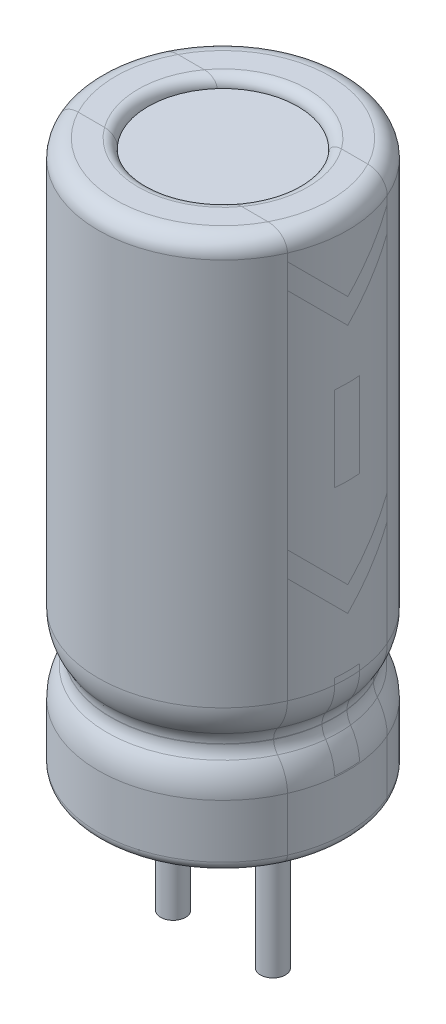
SolidWorks part; units mm, degrees
ref_plane "Front Plane" through (0, 0, 0) normal (0, 0, 1) x (1, 0, 0)
ref_plane "Top Plane" through (0, 0, 0) normal (0, 1, 0) x (1, 0, 0)
ref_plane "Right Plane" through (0, 0, 0) normal (1, 0, 0) x (0, 0, -1)
sketch "Эскиз1" plane through (0, 0, 0) normal (0, 0, 1) x (1, 0, 0)
  line L0 (0, 39.0662) -> (0, -46.657) construction
  line L1 (-41.2396, 0) -> (33.4802, 0) construction
  line L2 (0, 0) -> (-2.5, 0)
  line L3 (-2.5, 0) -> (-2.5, 1.7)
  line L4 (-2.5, 1.7) -> (-2.25, 1.7)
  line L5 (-2.25, 1.7) -> (-2.25, 2.45)
  line L6 (-2.25, 2.45) -> (-2.5, 2.45)
  line L7 (-2.5, 2.45) -> (-2.5, 11)
  line L8 (-2.5, 11) -> (0, 11)
  line L9 (0, 11) -> (0, 0)
  dimension "D1" = 2.5
  dimension "D2" = 11
  dimension "D3" = 1.7
  dimension "D4" = 0.75
  dimension "D5" = 2.5
  dimension "D6" = 0.25
revolve "Повернуть2" add sketch "Эскиз1" angle 360 about L0
fillet "Скругление12" radius 0.4 2 edges at (0, 2.45, 2.25) (0, 1.7, 2.25)
fillet "Скругление13" radius 1 1 edges at (0, 2.45, 2.5)
fillet "Скругление14" radius 1 1 edges at (0, 1.7, 2.5)
sketch "Эскиз3" plane through (0, 0, 0) normal (0, -1, 0) x (1, 0, 0)
  circle A0 centre (0, 0) radius 1.75
  dimension "D1" = 3.5
extrude "Вырез-Вытянуть1" cut sketch "Эскиз3" against normal blind 0.8
fillet "Скругление15" radius 0.2 1 edges at (0, 0, 2.5)
fillet "Скругление16" radius 0.1 1 edges at (0, 0, -1.75)
sketch "Эскиз4" plane through (0, 0.8, 0) normal (0, -1, 0) x (1, 0, 0)
  circle A0 centre (0, 0) radius 1.75
  dimension "D1" = 3.5
extrude "Бобышка-Вытянуть3" add sketch "Эскиз4" along normal blind 0.7
sketch "Эскиз5" plane through (0, 0.1, 0) normal (0, -1, 0) x (1, 0, 0)
  line L0 (-2.6693, 0) -> (2.9946, 0) construction
  line L1 (0, 2.8285) -> (0, -2.6825) construction
  circle A0 centre (-1, 0) radius 0.25
  circle A1 centre (1, 0) radius 0.25
  dimension "D1" = 0.5
  dimension "D2" = 1
extrude "Бобышка-Вытянуть4" add sketch "Эскиз5" along normal blind 3
sketch "Эскиз6" plane through (0, 11, 0) normal (0, 1, 0) x (1, 0, 0)
  circle A0 centre (0, 0) radius 1.5
  dimension "D1" = 3
extrude "Вырез-Вытянуть2" cut sketch "Эскиз6" against normal blind 0.3
sketch "Эскиз7" plane through (0, 10.7, 0) normal (0, 1, 0) x (1, 0, 0)
  circle A0 centre (0, 0) radius 1.75
  dimension "D1" = 3.5
extrude "Бобышка-Вытянуть5" add sketch "Эскиз7" along normal blind 0.1
fillet "Скругление17" radius 0.2 1 edges at (0, 11, 1.5)
fillet "Скругление18" radius 0.35 1 edges at (0, 11, 2.5)
ref_plane "Плоскость3" through (3, 0, 0) normal (1, 0, 0) x (0, 0, -1)
sketch "Эскиз10" plane through (3, 0, 0) normal (1, 0, 0) x (0, 0, -1)
  line L0 (1.7, 11) -> (-1.7, 11) construction
  line L1 (-1, 11) -> (1, 11) construction
  line L2 (-1, 11) -> (-1, 0)
  line L3 (-1, 0) -> (1, 0)
  line L4 (1, 11) -> (1, 0)
  line L5 (-2.3, 0) -> (2.3, 0) construction
  line L6 (0, 0) -> (0, 12.395) construction
  line L7 (-0.25, 8) -> (0.25, 8)
  line L8 (-0.25, 8) -> (-0.25, 6.3)
  line L9 (-0.25, 6.3) -> (0.25, 6.3)
  line L10 (0.25, 8) -> (0.25, 6.3)
  line L11 (-0.25, 8) -> (0.25, 6.3) construction
  line L12 (-0.25, 6.3) -> (0.25, 8) construction
  line L13 (-1, 10.5) -> (0, 9.5)
  line L14 (0, 9.5) -> (1, 10.5)
  line L15 (1, 10.5) -> (1, 10)
  line L16 (1, 10) -> (0, 9)
  line L17 (0, 9) -> (-1, 10)
  line L18 (-1, 10) -> (-1, 10.5)
  line L19 (-0.25, 3) -> (-0.25, 1.3)
  line L20 (-0.25, 3) -> (0.25, 3)
  line L21 (0.25, 3) -> (0.25, 1.3)
  line L22 (-0.25, 1.3) -> (0.25, 1.3)
  line L23 (-1, 5) -> (-1, 5.5)
  line L24 (-1, 5.5) -> (0, 4.5)
  line L25 (0, 4.5) -> (1, 5.5)
  line L26 (1, 5.5) -> (1, 5)
  line L27 (1, 5) -> (0, 4)
  line L28 (0, 4) -> (-1, 5)
  point P8 (0, 7.15)
  point P17 (0, 8)
  point P18 (0, 11)
  dimension "D1" = 2
  dimension "D2" = 3
  dimension "D3" = 0.5
  dimension "D4" = 1.7
  dimension "D5" = 0.5
  dimension "D6" = 0.5
  dimension "D7" = 0.5
  dimension "D8" = 2
split line "Разделяющая линия3"
sketch "Эскиз11" [suppressed] plane through (0, 10.9, 0) normal (0, 1, 0) x (1, 0, 0)
  line L0 (0, 2.7987) -> (0, -2.7757) construction
  line L1 (2.6925, 0) -> (-2.9822, 0) construction
  line L2 (-0.25, 1.7321) -> (-0.25, 0.25)
  line L3 (-0.25, 0.25) -> (-1.7321, 0.25)
  line L4 (0.25, 0.25) -> (1.7321, 0.25)
  line L5 (0.25, 1.7321) -> (0.25, 0.25)
  line L6 (0.25, -0.25) -> (1.7321, -0.25)
  line L7 (0.25, -1.7321) -> (0.25, -0.25)
  line L8 (-0.25, -0.25) -> (-1.7321, -0.25)
  line L9 (-0.25, -1.7321) -> (-0.25, -0.25)
  arc A0 (-1.4361, -1) -> (1.4361, -1) centre (0, 0) ccw construction
  arc A1 (1.4361, -1) -> (1.4361, 1) centre (0, 0) ccw construction
  arc A2 (1.4361, 1) -> (-1.4361, 1) centre (0, 0) ccw construction
  arc A3 (-1.4361, 1) -> (-1.4361, -1) centre (0, 0) ccw construction
  arc A4 (-0.25, -1.7321) -> (0.25, -1.7321) centre (0, 0) ccw
  arc A5 (1.7321, -0.25) -> (1.7321, 0.25) centre (0, 0) ccw
  arc A6 (0.25, 1.7321) -> (-0.25, 1.7321) centre (0, 0) ccw
  arc A7 (-1.7321, 0.25) -> (-1.7321, -0.25) centre (0, 0) ccw
  dimension "D1" = 0.25
  dimension "D2" = 0.25
extrude "Вырез-Вытянуть3" [suppressed] cut sketch "Эскиз11" against normal blind 0.11
fillet "Скругление19" [suppressed] radius 0.07
